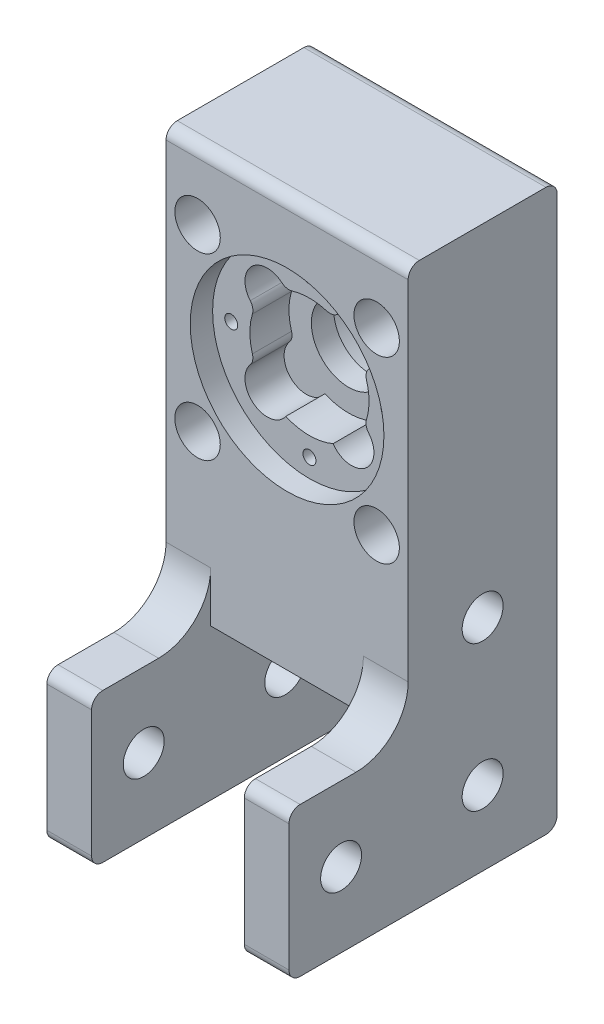
SolidWorks part; units mm, degrees
ref_plane "Front plane" through (0, 0, 0) normal (0, 0, 1) x (1, 0, 0)
ref_plane "Top plane" through (0, 0, 0) normal (0, 1, 0) x (1, 0, 0)
ref_plane "Right plane" through (0, 0, 0) normal (1, 0, 0) x (0, 0, -1)
ref_axis "Axis X" through (0, 0, 0) along (1, 0, 0)
ref_axis "Axis Y" through (0, 0, 0) along (0, 1, 0)
ref_axis "Axis Z" through (0, 0, 0) along (0, 0, 1)
sketch "Sketch1" plane through (0, 0, 0) normal (1, 0, 0) x (0, 0, -1)
  line L1 (10, 65.25) -> (-10, 65.25)
  line L2 (10, 65.25) -> (10, 10.25)
  line L3 (10, 10.25) -> (-10, 10.25)
  line L4 (-10, 65.25) -> (-10, 10.25)
  line L5 (10, 65.25) -> (-10, 10.25) construction
  line L6 (10, 10.25) -> (-10, 65.25) construction
  point P0 (0, 37.75)
  dimension "D1" = 10.25
  dimension "D2" = 20
  dimension "D3" = 55
extrude "Extrude1" add sketch "Sketch1" along normal blind 10.25 and the other way blind 10.25
sketch "Sketch2" plane through (10.25, 0, 0) normal (1, 0, 0) x (0, 0, -1)
  line L0 (10, 10.25) -> (10, 65.25) construction
  line L1 (26, 10) -> (17, 10)
  line L2 (26, 10) -> (26, -10)
  line L3 (26, -10) -> (-26, -10)
  line L4 (-26, 10) -> (-26, -10)
  line L5 (26, 10) -> (-26, -10) construction
  line L6 (26, -10) -> (-26, 10) construction
  line L7 (-10, 65.25) -> (10, 65.25)
  line L8 (-10, 65.25) -> (-10, 17)
  line L9 (-10, 10) -> (10, 10) construction
  line L10 (10, 65.25) -> (10, 17)
  line L11 (-17, 10) -> (-26, 10)
  line L12 (10, 10) -> (-10, 10) construction
  arc A0 (17, 10) -> (10, 17) centre (17, 17) cw
  arc A1 (-17, 10) -> (-10, 17) centre (-17, 17) ccw
  point P0 (0, 0)
  dimension "D3" = 7
  dimension "D1" = 20
  dimension "D2" = 52
extrude "Extrude2" add sketch "Sketch2" along normal blind 6
mirror "Mirror2" about plane through (0, 0, 0) normal (1, 0, 0) of "Extrude2"
sketch "Sketch4" plane through (16.25, 0, 0) normal (1, 0, 0) x (0, 0, -1)
  line L0 (0, 2.75) -> (0, -2.75) construction
  circle A0 centre (0, 0) radius 2.75
  circle A1 centre (19, 0) radius 2.75
  circle A2 centre (-19, 0) radius 2.75
  circle A3 centre (0, 19.5) radius 2.75
  circle A4 centre (0, 51.75) radius 2.75 construction
  dimension "D1" = 5.5
  dimension "D2" = 5.5
  dimension "D4" = 5.5
  dimension "D5" = 5.5
  dimension "D3" = 19
  dimension "D6" = 32.25
  dimension "D7" = 19.5
extrude "Extrude3" cut sketch "Sketch4" against normal through all
sketch "Sketch5" plane through (0, 0, 10) normal (0, 0, 1) x (1, 0, 0)
  line L0 (-16.25, 19.5) -> (16.25, 19.5) construction
  line L1 (-16.25, 65.25) -> (-16.25, 17) construction
  line L2 (16.25, 65.25) -> (16.25, 17) construction
  line L3 (-16.25, 22.25) -> (16.25, 22.25) construction
  line L4 (-16.25, 16.75) -> (16.25, 16.75) construction
  line L5 (-16.25, 54.5) -> (16.25, 54.5) construction
  line L6 (-16.25, 51.75) -> (16.25, 51.75) construction
  line L7 (-16.25, 49) -> (16.25, 49) construction
  line L8 (-5, 44) -> (5, 44) construction
  line L9 (-10.25, 10) -> (10.25, 10) construction
  line L10 (-10.25, 10) -> (-10.25, -10) construction
  line L11 (10.25, 10) -> (10.25, -10) construction
  circle A0 centre (0, 44) radius 5
  dimension "D1" = 5.5
  dimension "D2" = 5.5
  dimension "D5" = 10
  dimension "D3" = 19.5
  dimension "D4" = 32.25
  dimension "D7" = 10
  dimension "D8" = 34
extrude "Extrude4" cut sketch "Sketch5" against normal through all
fillet "Fillet2" radius 1.5 10 edges at (13.25, -10, 26) (13.25, 10, 26) (-13.25, 10, 26) (-13.25, -10, 26) (-13.25, -10, -26) (13.25, -10, -26) (13.25, 10, -26) (-13.25, 10, -26) (0, 65.25, 10) (0, 65.25, -10)
sketch "Эскиз1" plane through (0, 0, -10) normal (0, 0, -1) x (-1, 0, 0)
  line L0 (-16.25, 17) -> (-16.25, 63.75) construction
  line L1 (16.25, -10) -> (-16.25, -10)
  line L2 (16.25, -10) -> (16.25, 63.75)
  line L3 (16.25, 63.75) -> (-16.25, 63.75)
  line L4 (-16.25, -10) -> (-16.25, 63.75)
  line L5 (16.25, -10) -> (-16.25, 63.75) construction
  line L6 (16.25, 63.75) -> (-16.25, -10) construction
  line L7 (16.25, 17) -> (16.25, 63.75) construction
  line L8 (16.25, 63.75) -> (-16.25, 63.75) construction
  line L9 (-10.25, -10) -> (-16.25, -10) construction
  point P0 (0, 26.875)
extrude "Вырез-Вытянуть1" cut sketch "Эскиз1" along normal through all
fillet "Скругление1" radius 1.5 2 edges at (13.25, -10, -10) (-13.25, -10, -10)
sketch "Эскиз2" plane through (0, 0, 10) normal (0, 0, 1) x (1, 0, 0)
  circle A0 centre (0, 44) radius 13
  dimension "D1" = 26
extrude "Вырез-Вытянуть2" cut sketch "Эскиз2" against normal blind 3
sketch "Эскиз3" plane through (0, 0, 7) normal (0, 0, 1) x (1, 0, 0)
  circle A0 centre (0, 44) radius 8
  arc A1 (-2.9468, 51.4375) -> (2.9468, 51.4375) centre (0, 52) cw construction
  arc A2 (3.1754, 51.3428) -> (7.3428, 47.1754) centre (5.6569, 49.6569) cw
  arc A3 (7.4375, 46.9468) -> (7.4375, 41.0532) centre (8, 44) cw construction
  arc A4 (7.3428, 40.8246) -> (3.1754, 36.6572) centre (5.6569, 38.3431) cw
  arc A5 (2.9468, 36.5625) -> (-2.9468, 36.5625) centre (0, 36) cw construction
  arc A6 (-3.1754, 36.6572) -> (-7.3428, 40.8246) centre (-5.6569, 38.3431) cw
  arc A7 (-7.4375, 41.0532) -> (-7.4375, 46.9468) centre (-8, 44) cw construction
  arc A8 (-7.3428, 47.1754) -> (-3.1754, 51.3428) centre (-5.6569, 49.6569) cw
  point P6 (0, 0)
  point P7 (0, 0)
  circle M11 centre (0, 44) radius 5
  dimension "D1" = 16
  dimension "D2" = 3
  dimension "D3" = 8
extrude "Вырез-Вытянуть3" cut sketch "Эскиз3" against normal blind 5.25 contours A0 M11 | A8 A0 | A2 A0 | A4 A0 | A6 A0 region at (7.6124, 42.4245, 7) region at (6.4817, 50.4817, 7) region at (6.4817, 37.5183, 7) region at (-6.4817, 50.4817, 7) region at (-6.4817, 37.5183, 7)
fillet "Скругление2" radius 1.5 6 edges at (-7.3428, 47.1754, 4.375) (-7.3428, 40.8246, 4.375) (7.3428, 40.8246, 4.375) (7.3428, 47.1754, 4.375) (3.1754, 51.3428, 4.375) (-3.1754, 51.3428, 4.375)
sketch "Эскиз4" plane through (0, 0, -10) normal (0, 0, -1) x (-1, 0, 0)
  circle A0 centre (0, 44) radius 10
  dimension "D1" = 20
extrude "Вырез-Вытянуть4" cut sketch "Эскиз4" against normal offset from surface (8.75 mm away) 3 up to face at (5, 44, 1.75)
sketch "Эскиз5" plane through (0, 0, 7) normal (0, 0, 1) x (1, 0, 0)
  circle A0 centre (0, 44) radius 10.5 construction
  circle A1 centre (0, 54.5) radius 0.875
  circle A2 centre (10.5, 44) radius 0.875
  circle A3 centre (0, 33.5) radius 0.875
  circle A4 centre (-10.5, 44) radius 0.875
  point P5 (0, 0)
  point P6 (0, 0)
  dimension "D1" = 21
  dimension "D2" = 1.75
  dimension "D3" = 4
extrude "Вырез-Вытянуть5" cut sketch "Эскиз5" against normal blind 8
sketch "Эскиз7" plane through (0, 0, 10) normal (0, 0, 1) x (1, 0, 0)
  line L1 (-12.0208, 56.0208) -> (12.0208, 56.0208) construction
  line L2 (-12.0208, 56.0208) -> (-12.0208, 31.9792) construction
  line L3 (-12.0208, 31.9792) -> (12.0208, 31.9792) construction
  line L4 (12.0208, 56.0208) -> (12.0208, 31.9792) construction
  line L5 (-12.0208, 56.0208) -> (12.0208, 31.9792) construction
  line L6 (-12.0208, 31.9792) -> (12.0208, 56.0208) construction
  circle A0 centre (0, 44) radius 17 construction
  circle A1 centre (-12.0208, 56.0208) radius 1.75
  circle A2 centre (12.0208, 56.0208) radius 1.75
  circle A3 centre (0, 44) radius 17 construction
  circle A4 centre (12.0208, 31.9792) radius 1.75
  circle A5 centre (0, 44) radius 17 construction
  circle A6 centre (-12.0208, 31.9792) radius 1.75
  circle A7 centre (0, 44) radius 17 construction
  point P8 (0, 0)
  dimension "D3" = 4
  dimension "D1" = 34
  dimension "D2" = 3.5
extrude "Вырез-Вытянуть6" cut sketch "Эскиз7" against normal through all
sketch "Эскиз8" plane through (0, 0, 10) normal (0, 0, 1) x (1, 0, 0)
  circle A0 centre (-12.0208, 56.0208) radius 3.05
  circle A1 centre (0, 44) radius 17 construction
  circle A2 centre (12.0208, 56.0208) radius 3.05
  circle A3 centre (12.0208, 31.9792) radius 3.05
  circle A4 centre (-12.0208, 31.9792) radius 3.05
  point P6 (0, 0)
  point P7 (0, 0)
  dimension "D1" = 6.1
extrude "Вырез-Вытянуть7" cut sketch "Эскиз8" against normal offset from surface (5 mm away) 15 up to face at (-10.2708, 31.9792, -10)
equation "\"print_offset\"= 0.5"
equation "\"prof_width\"= 20'Aluminium profile parameters"
equation "\"D1@Sketch1\"=(\"prof_width\"+\"print_offset\")/2"
equation "\"D3@Sketch1\" = 55.00"
equation "\"D1@Extrude1\"=(\"prof_width\"+\"print_offset\")/2"
equation "\"D2@Extrude1\"=(\"prof_width\"+\"print_offset\")/2"
equation "\"D1@Sketch2\"=\"prof_width\""
equation "\"D1@Sketch4\"=\"print_offset\"+5"
equation "\"D2@Sketch4\"=\"D1@Sketch4\""
equation "\"D4@Sketch4\"=\"D1@Sketch4\""
equation "\"D5@Sketch4\"=\"D1@Sketch4\""
equation "\"D2@Sketch5\"=\"D1@Sketch5\""
equation "\"D1@Sketch5\" = \"print_offset\" + 5.00"
equation "\"D7@Sketch5\"=\"prof_width\"/2"
equation "\"radial_bearing_d1\"= 7.7"
equation "\"radial_bearing_d2\"= 16"
equation "\"radial_bearing_h\"= 5"
equation "\"shaft_d\"= 6"
equation "\"shaft_h\" = 50"
equation "\"central_hole_d\"= 20"
equation "\"sitting_screws_d\"= 34"
equation "\"screw_d\"= 2"
equation "\"screw_hh_d\"= 3.4"
equation "\"screw_h\"= 8"
equation "\"screw_hh_h\"= 2"
equation "\"motor_screw_d\"= 3"
equation "\"motor_screw_hh_d\"= 5.6"
equation "\"motor_screw_h\" = 20"
equation "\"motor_screw_hh_h\"= 2"
equation "\"motor_nut_d\"= 5.4"
equation "\"motor_nut_h\"= 2.8"
equation "\"D1@Эскиз2\"=\"radial_bearing_d2\"+10"
equation "\"D1@Эскиз3\"=\"radial_bearing_d2\""
equation "\"D1@Вырез-Вытянуть3\"=\"radial_bearing_h\"+\"print_offset\"/2"
equation "\"D1@Эскиз4\"=\"central_hole_d\""
equation "\"D1@Эскиз5\"=\"radial_bearing_d2\"+5"
equation "\"D2@Эскиз5\"=\"screw_d\"-\"print_offset\"/2"
equation "\"D1@Вырез-Вытянуть5\"=\"screw_h\""
equation "\"D1@Эскиз7\"=\"sitting_screws_d\""
equation "\"D2@Эскиз7\"=\"motor_screw_d\"+\"print_offset\""
equation "\"D1@Вырез-Вытянуть6\"=\"motor_screw_h\"-5"
equation "\"D1@Эскиз8\"=\"motor_screw_hh_d\"+\"print_offset\""
equation "\"D1@Вырез-Вытянуть7\"=\"motor_screw_h\"-5"
